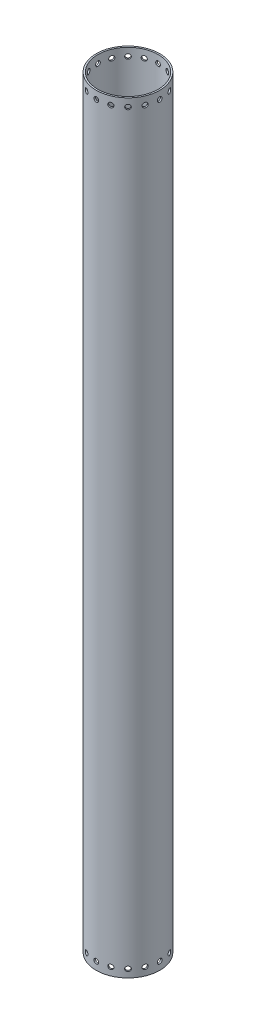
SolidWorks part; units mm, degrees
material "6061-T6 (SS)"
ref_plane "Front Plane" through (0, 0, 0) normal (0, 0, 1) x (1, 0, 0)
ref_plane "Top Plane" through (0, 0, 0) normal (0, 1, 0) x (1, 0, 0)
ref_plane "Right Plane" through (0, 0, 0) normal (1, 0, 0) x (0, 0, -1)
sketch "Sketch1" plane through (0, 0, 0) normal (0, 1, 0) x (1, 0, 0)
  circle A0 centre (0, 0) radius 63.5
  circle A1 centre (0, 0) radius 60.325
extrude "Boss-Extrude1" add sketch "Sketch1" along normal blind 1524
ref_plane "Plane1" through (0, 0, 63.5) normal (0, 0, 1) x (1, 0, 0)
sketch "Sketch11" plane through (0, 0, 63.5) normal (0, 0, 1) x (1, 0, 0)
  line L0 (-63.5, 0) -> (63.5, 0) construction
  point P4 (0, 15.875)
  dimension "D1" = 15.875
hole_wizard "3/8 (0.375) Diameter Hole1" positions "Sketch15" profile "Sketch16" hole size "3/8" standard "ANSI Inch" end condition through all
sketch "Sketch15" plane through (0, 0, 63.5) normal (0, 0, 1) x (1, 0, 0)
  point P0 (0, 15.875)
sketch "Sketch16" plane through (0, 15.875, 63.5) normal (1, 0, 0) x (0, -1, 0)
  line L0 (0, 0) -> (0, 127)
  line L1 (0, 127) -> (4.7625, 127)
  line L2 (4.7625, 127) -> (4.7625, 0)
  line L5 (4.7625, 0) -> (0, 0)
  line L11 (0, -6.35) -> (0, 107.95) construction
  dimension "Thru Hole Dia." = 9.525
  dimension "Thru Hole Depth" = 127
sketch "Sketch17" plane through (0, 0, 0) normal (0, 0, 1) x (1, 0, 0)
  line L0 (0, 0) -> (0, 43.95) construction
pattern_circular "CirPattern1" count 16 over 360 about axis through (0, 0, 0) along (0, 1, 0) of "3/8 (0.375) Diameter Hole1"
ref_plane "Plane2" through (0, 15.875, 0) normal (0, 1, 0) x (1, 0, 0)
sketch "Sketch18" plane through (0, 0, 63.5) normal (0, 0, 1) x (1, 0, 0)
  line L0 (63.5, 1524) -> (-63.5, 1524) construction
  point P5 (0, 0)
  point P6 (0, 1508.125)
  dimension "D1" = 15.875
hole_wizard "3/8 (0.375) Diameter Hole2" positions "Sketch19" profile "Sketch21" hole size "3/8" standard "ANSI Inch" end condition through all
sketch "Sketch19" plane through (0, 0, 63.5) normal (0, 0, 1) x (1, 0, 0)
  point P0 (0, 1508.125)
  point P4 (0, 1508.125)
sketch "Sketch21" plane through (0, 1508.125, 63.5) normal (1, 0, 0) x (0, -1, 0)
  line L0 (0, 0) -> (0, 127)
  line L1 (0, 127) -> (4.7625, 127)
  line L2 (4.7625, 127) -> (4.7625, 0)
  line L5 (4.7625, 0) -> (0, 0)
  line L11 (0, -6.35) -> (0, 107.95) construction
  dimension "Thru Hole Dia." = 9.525
  dimension "Thru Hole Depth" = 127
sketch "Sketch22" plane through (0, 0, 0) normal (0, 0, 1) x (1, 0, 0)
  line L0 (0, 0) -> (0, 1524) construction
  line L1 (60.325, 1524) -> (-60.325, 1524) construction
  point P4 (0, 0)
  point P5 (0, 1524)
pattern_circular "CirPattern2" count 16 over 360 about axis through (0, 0, 0) along (0, 1, 0) of "3/8 (0.375) Diameter Hole2" reverse direction yes
ref_plane "Plane3" through (0, 1508.125, 0) normal (0, 1, 0) x (1, 0, 0)
